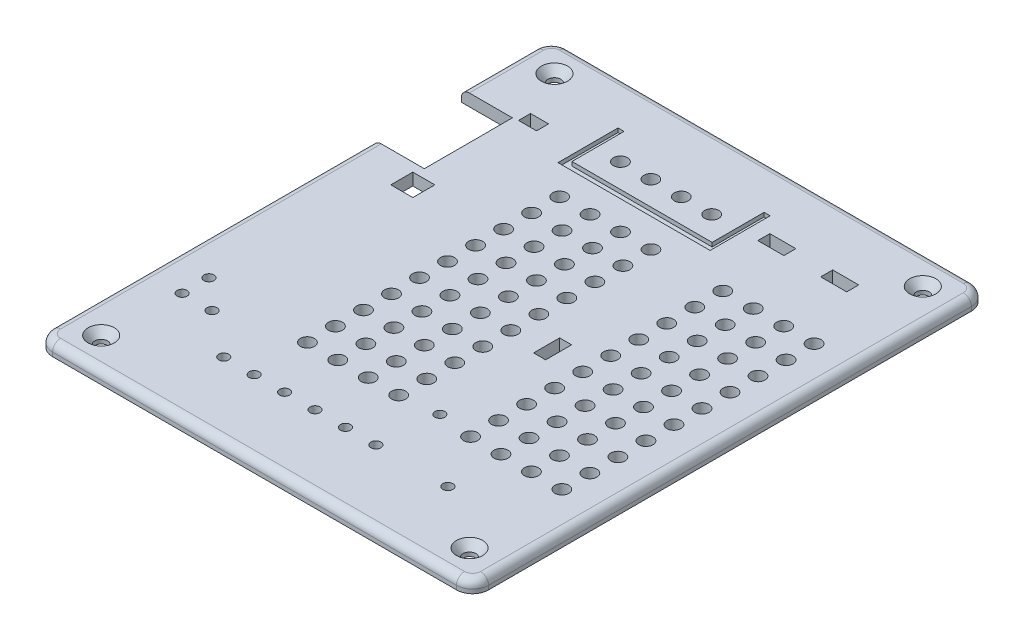
SolidWorks part; units mm, degrees
ref_plane "Přední rovina" through (0, 0, 0) normal (0, 0, 1) x (1, 0, 0)
ref_plane "Horní rovina" through (0, 0, 0) normal (0, 1, 0) x (1, 0, 0)
ref_plane "Pravá rovina" through (0, 0, 0) normal (1, 0, 0) x (0, 0, -1)
sketch "Skica1" plane through (0, 0, 0) normal (0, 1, 0) x (1, 0, 0)
  line L1 (-54.445, -64.3) -> (54.445, -64.3)
  line L2 (-54.445, -64.3) -> (-54.445, 64.3)
  line L3 (-54.445, 64.3) -> (54.445, 64.3)
  line L4 (54.445, -64.3) -> (54.445, 64.3)
  line L5 (-54.445, -64.3) -> (54.445, 64.3) construction
  line L6 (-54.445, 64.3) -> (54.445, -64.3) construction
  point P0 (0, 0)
  dimension "D1" = 108.89
  dimension "D2" = 128.6
extrude "Přidat vysunutím1" add sketch "Skica1" along normal blind 3
fillet "Zaoblit1" radius 4 4 edges at (54.445, 1.5, -64.3) (54.445, 1.5, 64.3) (-54.445, 1.5, -64.3) (-54.445, 1.5, 64.3)
fillet "Zaoblit2" radius 2 8 edges at (53.2734, 3, 63.1284) (0, 3, 64.3) (-53.2734, 3, 63.1284) (-54.445, 3, 0) (-53.2734, 3, -63.1284) (0, 3, -64.3) (53.2734, 3, -63.1284) (54.445, 3, 0)
sketch "Skica2" plane through (0, 0, 0) normal (0, -1, 0) x (1, 0, 0)
  line L0 (0, 68.8192) -> (0, -71.6902) construction
  line L1 (-80.8942, 0) -> (91.0271, 0) construction
  circle A0 centre (-46, 56.6) radius 1.6
  dimension "D1" = 3.2
  dimension "D2" = 46
  dimension "D3" = 56.6
extrude "Odebrat vysunutím1" cut sketch "Skica2" against normal blind 3
pattern_linear "LinPole1" count 2 spacing 113.2 along (0, 0, -1) count 2 spacing 92 along (1, 0, 0) of "Odebrat vysunutím1"
chamfer "Zkosení1" distance 2 angle 40 4 edges at (46, 3, 55) (46, 3, -58.2) (-46, 3, -58.2) (-46, 3, 55) first distance on face at (46, 3, 55) first distance on face at (46, 3, -58.2) first distance on face at (-46, 3, -58.2) first distance on face at (-46, 3, 55)
sketch "Skica3" plane through (0, 3, 0) normal (0, 1, 0) x (1, 0, 0)
  line L3 (-50, -50) -> (50, -50) construction
  line L4 (-50, -50) -> (-50, 50) construction
  line L5 (-50, 50) -> (50, 50) construction
  line L6 (50, -50) -> (50, 50) construction
  line L7 (-50, -50) -> (50, 50) construction
  line L8 (-50, 50) -> (50, -50) construction
  circle A0 centre (44.83, -32.38) radius 1.75
  circle A1 centre (4.08, -32.38) radius 1.75
  circle A2 centre (4.08, 45.8) radius 1.75
  point P7 (0, 0)
  dimension "D2" = 3.5
  dimension "D6" = 3.5
  dimension "D11" = 3.5
  dimension "D1" = 5.17
  dimension "D3" = 17.62
  dimension "D4" = 100
  dimension "D5" = 100
  dimension "D7" = 45.92
  dimension "D8" = 17.62
  dimension "D9" = 45.92
  dimension "D10" = 4.2
extrude "Odebrat vysunutím3" cut sketch "Skica3" against normal blind 4 contours A0 region at (44.83, 3, 32.38)
pattern_linear "LinPole3" count 10 spacing 7 along (0, 0, -1) count 4 spacing 7.6 along (-1, 0, 0) of "Odebrat vysunutím3"
extrude "Odebrat vysunutím4" cut sketch "Skica3<3>" against normal blind 4 contours A1 region at (4.08, 3, 32.38)
sketch "Skica3<3>" plane through (0, 3, 0) normal (0, 1, 0) x (1, 0, 0) same geometry as "Skica3"
pattern_linear "LinPole4" count 10 spacing 7 along (0, 0, -1) count 4 spacing 7.6 along (-1, 0, 0) of "Odebrat vysunutím4"
extrude "Odebrat vysunutím5" cut sketch "Skica3<4>" against normal blind 10
sketch "Skica3<4>" plane through (0, 3, 0) normal (0, 1, 0) x (1, 0, 0) same geometry as "Skica3"
pattern_linear "LinPole5" count 4 spacing 7.6 along (-1, 0, 0) of "Odebrat vysunutím5"
sketch "Skica4" plane through (0, 3, 0) normal (0, 1, 0) x (1, 0, 0)
  line L1 (-50, -50) -> (50, -50) construction
  line L2 (-50, -50) -> (-50, 50) construction
  line L3 (-50, 50) -> (50, 50) construction
  line L4 (50, -50) -> (50, 50) construction
  line L5 (-50, -50) -> (50, 50) construction
  line L6 (-50, 50) -> (50, -50) construction
  line L7 (15.5, 48.9) -> (22, 48.9)
  line L8 (15.5, 48.9) -> (15.5, 45.9)
  line L9 (15.5, 45.9) -> (22, 45.9)
  line L10 (22, 48.9) -> (22, 45.9)
  line L11 (15.5, 48.9) -> (22, 45.9) construction
  line L12 (15.5, 45.9) -> (22, 48.9) construction
  line L13 (31.2, 48.9) -> (37.7, 48.9)
  line L14 (31.2, 48.9) -> (31.2, 45.9)
  line L15 (31.2, 45.9) -> (37.7, 45.9)
  line L16 (37.7, 48.9) -> (37.7, 45.9)
  line L17 (31.2, 48.9) -> (37.7, 45.9) construction
  line L18 (31.2, 45.9) -> (37.7, 48.9) construction
  line L19 (11.8, 0.1) -> (14.8, 0.1)
  line L20 (11.8, 0.1) -> (11.8, -6.4)
  line L21 (11.8, -6.4) -> (14.8, -6.4)
  line L22 (14.8, 0.1) -> (14.8, -6.4)
  line L23 (11.8, 0.1) -> (14.8, -6.4) construction
  line L24 (11.8, -6.4) -> (14.8, 0.1) construction
  circle A0 centre (13.38, -31.4) radius 1.25
  circle A2 centre (30, -46) radius 1.25
  circle A3 centre (-45, -37.4) radius 1.25
  circle A4 centre (-45, -30.7) radius 1.25
  circle A5 centre (-37.52, -37.4) radius 1.25
  point P0 (0, 0)
  point P6 (18.75, 47.4)
  point P11 (34.45, 47.4)
  point P16 (13.3, -3.15)
  point P21 (13.3, 0.1)
  dimension "D13" = 2.5
  dimension "D16" = 12.48
  dimension "D17" = 2.5
  dimension "D23" = 2.5
  dimension "D24" = 2.5
  dimension "D25" = 2.5
  dimension "D1" = 100
  dimension "D2" = 100
  dimension "D3" = 3
  dimension "D4" = 6.5
  dimension "D5" = 1.1
  dimension "D6" = 1.1
  dimension "D7" = 12.3
  dimension "D8" = 28
  dimension "D9" = 35.2
  dimension "D10" = 49.9
  dimension "D11" = 36.62
  dimension "D12" = 18.6
  dimension "D14" = 5
  dimension "D15" = 5
  dimension "D18" = 20
  dimension "D19" = 4
  dimension "D20" = 80.7
  dimension "D21" = 87.4
  dimension "D22" = 87.4
extrude "Odebrat vysunutím6" cut sketch "Skica4" against normal blind 10
sketch "Skica5" plane through (0, 3, 0) normal (0, 1, 0) x (1, 0, 0)
  line L1 (-50, 50) -> (50, 50) construction
  line L2 (-50, 50) -> (-50, -50) construction
  line L3 (-50, -50) -> (50, -50) construction
  line L4 (50, 50) -> (50, -50) construction
  line L5 (-50, 50) -> (50, -50) construction
  line L6 (-50, -50) -> (50, 50) construction
  circle A0 centre (-26, -46) radius 1.25
  point P0 (0, 0)
  dimension "D5" = 2.5
  dimension "D1" = 100
  dimension "D2" = 100
  dimension "D3" = 4
  dimension "D4" = 76
extrude "Odebrat vysunutím7" cut sketch "Skica5" against normal blind 10
pattern_linear "LinPole6" count 6 spacing 7.6 along (1, 0, 0) of "Odebrat vysunutím7"
sketch "Skica6" plane through (0, 3, 0) normal (0, 1, 0) x (1, 0, 0)
  line L0 (-54.445, -60.3) -> (-54.445, 60.3) construction
  line L1 (-42.39, 17.62) -> (-36.89, 17.62)
  line L2 (-42.39, 17.62) -> (-42.39, 12.12)
  line L3 (-42.39, 12.12) -> (-36.89, 12.12)
  line L4 (-36.89, 17.62) -> (-36.89, 12.12)
  line L5 (-42.39, 17.62) -> (-36.89, 12.12) construction
  line L6 (-42.39, 12.12) -> (-36.89, 17.62) construction
  line L7 (-41.7, 41.8) -> (-54.445, 41.8)
  line L8 (-41.7, 41.8) -> (-41.7, 19.8)
  line L9 (-41.7, 19.8) -> (-54.445, 19.8)
  line L10 (-54.445, 41.8) -> (-54.445, 19.8)
  line L11 (-41.7, 41.8) -> (-54.445, 19.8) construction
  line L12 (-41.7, 19.8) -> (-54.445, 41.8) construction
  line L14 (-50, 50) -> (50, 50) construction
  line L15 (-50, 50) -> (-50, -50) construction
  line L16 (-50, -50) -> (50, -50) construction
  line L17 (50, 50) -> (50, -50) construction
  line L18 (-50, 50) -> (50, -50) construction
  line L19 (-50, -50) -> (50, 50) construction
  line L20 (-40.37, 45) -> (-35.87, 45)
  line L21 (-40.37, 45) -> (-40.37, 42)
  line L22 (-40.37, 42) -> (-35.87, 42)
  line L23 (-35.87, 45) -> (-35.87, 42)
  line L24 (-40.37, 45) -> (-35.87, 42) construction
  line L25 (-40.37, 42) -> (-35.87, 45) construction
  point P0 (-39.64, 14.87)
  point P5 (-48.0725, 30.8)
  point P12 (0, 0)
  point P18 (-48.0725, 41.8)
  point P20 (-38.12, 43.5)
  dimension "D1" = 100
  dimension "D2" = 100
  dimension "D3" = 10.36
  dimension "D4" = 35.13
  dimension "D5" = 5.5
  dimension "D6" = 8.2
  dimension "D7" = 30.2
  dimension "D8" = 8.3
  dimension "D9" = 6.5
  dimension "D10" = 11.88
  dimension "D11" = 4.5
  dimension "D12" = 3
extrude "Odebrat vysunutím8" cut sketch "Skica6" against normal blind 10 contours L4 L1 L2 L3 | L23 L20 L21 L22 | L7 L10 L9 L8 region at (-39.64, 3, -14.87) region at (-38.12, 3, -43.5)
sketch "Skica7" plane through (0, 3, 0) normal (0, 1, 0) x (1, 0, 0)
  line L1 (-24.82, 39.8) -> (10.18, 39.8)
  line L2 (-24.82, 39.8) -> (-24.82, 37.8)
  line L3 (-24.82, 37.8) -> (10.18, 37.8)
  line L4 (10.18, 39.8) -> (10.18, 37.8)
  line L5 (-26.32, 52.8) -> (-24.82, 52.8)
  line L6 (-26.32, 52.8) -> (-26.32, 37.8)
  line L7 (-26.32, 37.8) -> (-24.82, 37.8)
  line L8 (-24.82, 52.8) -> (-24.82, 37.8)
  line L9 (11.68, 52.8) -> (10.18, 52.8)
  line L10 (11.68, 52.8) -> (11.68, 37.8)
  line L11 (11.68, 37.8) -> (10.18, 37.8)
  line L12 (10.18, 52.8) -> (10.18, 37.8)
  circle A0 centre (-11.12, 45.8) radius 1.75 construction
  circle A1 centre (-18.72, 45.8) radius 1.75 construction
  dimension "D2" = 6
  dimension "D6" = 2
  dimension "D1" = 35
  dimension "D3" = 15
  dimension "D4" = 1.5
  dimension "D5" = 6.1
extrude "Odebrat vysunutím9" cut sketch "Skica7" against normal blind 1 contours L4 L1 L2 L3 | L8 L5 L6 L7 L2 | L9 L12 L4 L11 L10 region at (-7.32, 3, -38.8) region at (-25.57, 3, -45.3) region at (10.93, 3, -45.3)
